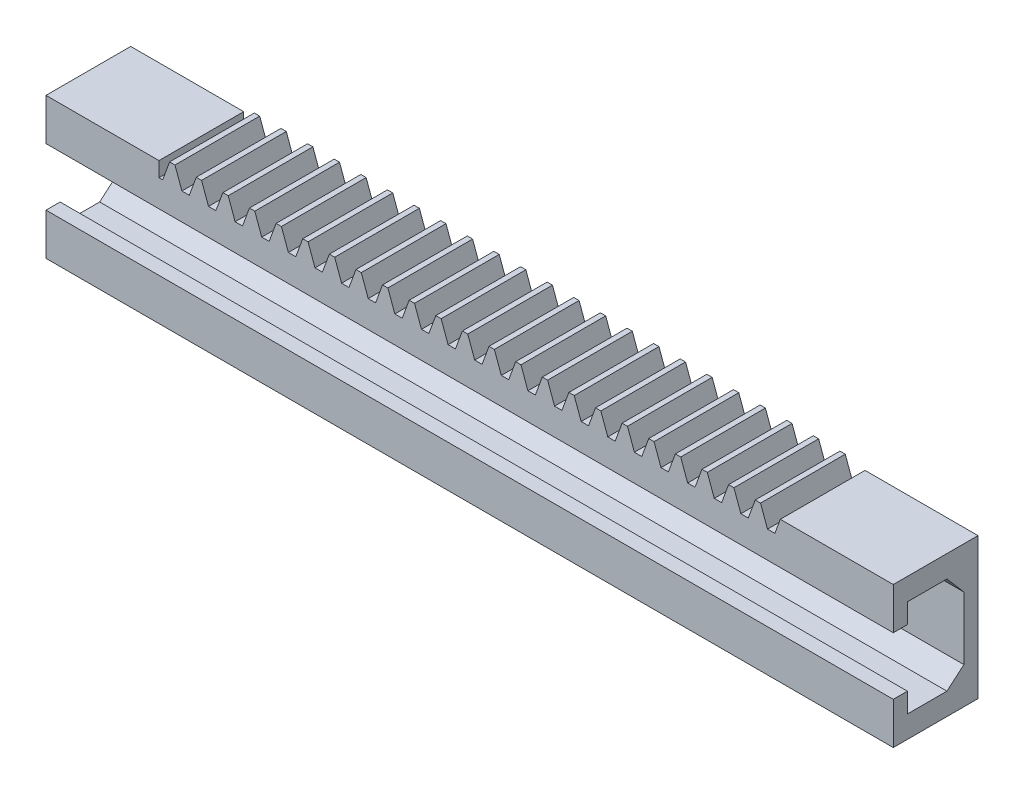
SolidWorks part; units mm, degrees
extrude "Blank" add sketch "BlankSke" against normal blind 15
sketch "BlankSke" plane through (0, 0, 0) normal (0, 0, 1) x (1, 0, 0)
  line L1 (0, 0) -> (110, 0)
  line L2 (0, 0) -> (0, 11.5)
  line L3 (0, 11.5) -> (110, 11.5)
  line L4 (110, 0) -> (110, 11.5)
  dimension "Length" = 110
ref_plane "Plane1" through (0, 0, 0) normal (0, 0, 1) x (1, 0, 0)
ref_plane "Plane2" through (0, 0, 0) normal (0, 1, 0) x (1, 0, 0)
ref_plane "Plane3" through (0, 0, 0) normal (1, 0, 0) x (0, 0, -1)
other "Configuration Table"
sketch "HoldingSke" plane through (0, 0, 0) normal (0, 1, 0) x (1, 0, 0)
  line L0 (0, 0) -> (0.0928, 0.6602)
  line L1 (-15, 0) -> (100, 0) construction
  line L2 (0, 0) -> (-2.1039, 2.3779)
  line L3 (0, 0) -> (-11.863, 4.5341)
  line L4 (0, 0) -> (7.8269, 3.6497)
  line L5 (0, 0) -> (-23.7986, -8.8762)
  line L6 (0, 0) -> (-10.5278, -7.1032)
  line L9 (-71.009, 38.7566) -> (32.3572, 76.3788)
  line L10 (-76.2, 3.8779) -> (-66.2, 3.8779)
  line L11 (0, 0) -> (-15, 0)
  line L12 (-76.2, 101.6) -> (-76.147, 101.6)
  line L13 (24.9733, 27.94) -> (52.9518, 28.4284)
  line L14 (24.9733, 27.94) -> (24.9743, 27.94)
  line L15 (24.9733, 27.94) -> (100.4006, 29.5858)
  circle A0 centre (0, 0) radius 19.05
  circle A1 centre (0, 0) radius 5
  circle A2 centre (0, 0) radius 12.7
  dimension "Num_teeth" = 25
  dimension "Width" = 15
  dimension "Length" = 110
  dimension "Pitch_height" = 10
sketch "TooCutSkeIll" plane through (0, 0, 0) normal (0, 0, 1) x (1, 0, 0)
  line L0 (-1.8687, 11.4605) -> (-0.7447, 8.3724)
  line L1 (-0.3914, 8.125) -> (0.3914, 8.125)
  line L2 (0.7447, 8.3724) -> (1.8687, 11.4605)
  line L3 (110, 11.5) -> (0, 11.5) construction
  line L4 (0, 0) -> (0, 64.897) construction
  line L5 (-13.208, 10) -> (12.954, 10) construction
  line L6 (0, 0) -> (110, 0) construction
  line L7 (1.3371, 10) -> (1.3371, 48.7463) construction
  line L8 (-1.3371, 10) -> (-1.3371, 48.7463) construction
  line L9 (1.9251, 11.5) -> (1.9251, 11.5254)
  line L10 (-1.9251, 11.5) -> (-1.9251, 11.5254)
  line L11 (-1.9251, 11.5254) -> (1.9251, 11.5254)
  arc A0 (0.3914, 8.125) -> (0.7447, 8.3724) centre (0.3914, 8.501) ccw
  arc A1 (-0.7447, 8.3724) -> (-0.3914, 8.125) centre (-0.3914, 8.501) ccw
  arc A2 (1.9251, 11.5) -> (1.8687, 11.4605) centre (1.9251, 11.44) ccw
  arc A3 (-1.8687, 11.4605) -> (-1.9251, 11.5) centre (-1.9251, 11.44) ccw
  dimension "Addendum_plus" = 1.5254
  dimension "Pitch_height" = 10
  dimension "Pressure_angle" = 20
  dimension "Gap_width" = 2.6742
  dimension "Dedendum" = 1.875
extrude "ToothCutIll" [suppressed] cut sketch "TooCutSkeIll" against normal through all
sketch "TooCutSkeSim" plane through (0, 0, 0) normal (0, 0, 1) x (1, 0, 0)
  line L0 (0.6547, 8.125) -> (-0.6547, 8.125)
  line L1 (1.8923, 11.5254) -> (0.6547, 8.125)
  line L2 (0, 17.4625) -> (0, 53.467) construction
  line L3 (1.8923, 11.5254) -> (-1.8923, 11.5254)
  line L6 (-1.8923, 11.5254) -> (-0.6547, 8.125)
  line L9 (-1.3371, 10) -> (1.3371, 10) construction
  line L10 (0, 0) -> (110, 0) construction
  line L11 (1.3371, 10) -> (1.3371, 53.467) construction
  line L12 (-1.3371, 10) -> (-1.3371, 53.467) construction
  dimension "Addendum_plus" = 1.5254
  dimension "Pitch_height" = 10
  dimension "Pressure_angle" = 20
  dimension "Gap_width" = 2.6742
  dimension "Dedendum" = 1.875
extrude "ToothCutSim" cut sketch "TooCutSkeSim" against normal through all
pattern_linear "TeethCuts" count 25 spacing 4.7124 along (1, 0, 0) of "ToothCutIll", "ToothCutSim"
sketch "Sketch1" plane through (110, 0, 0) normal (1, 0, 0) x (0, 0, -1)
  line L1 (0, 10.7637) -> (15, 10.7637)
  line L2 (0, 10.7637) -> (0, 0)
  line L3 (0, 0) -> (15, 0)
  line L4 (15, 10.7637) -> (15, 0)
extrude "Boss-Extrude1" add sketch "Sketch1" along normal blind 20
sketch "Sketch4" plane through (0, 0, 0) normal (-1, 0, 0) x (0, 0, 1)
  line L0 (-15, 8.125) -> (-15, 11.5) construction
  line L1 (0, 0) -> (-15, 0)
  line L2 (0, 0) -> (0, 10.764)
  line L3 (0, 10.764) -> (-15, 10.764)
  line L4 (-15, 0) -> (-15, 10.764)
extrude "Boss-Extrude2" add sketch "Sketch4" along normal blind 20
sketch "Sketch5" plane through (0, 0, 0) normal (0, -1, 0) x (1, 0, 0)
  line L1 (-20, -15) -> (130, -15)
  line L2 (-20, -15) -> (-20, 0)
  line L3 (-20, 0) -> (130, 0)
  line L4 (130, -15) -> (130, 0)
extrude "Boss-Extrude3" add sketch "Sketch5" along normal blind 14.236
sketch "Sketch7" plane through (-20, 0, 0) normal (-1, 0, 0) x (0, 0, 1)
  line L0 (-2.5, -6.836) -> (-2.5, -10.336)
  line L2 (-9.5, -10.336) -> (-7.5, -10.336)
  line L5 (-7.5, -10.336) -> (-2.5, -10.336)
  line L7 (0, -6.836) -> (0, 3.364)
  line L8 (-2.5, 6.864) -> (-9.5, 6.864)
  line L9 (-15, 10.764) -> (-15, -14.236) construction
  line L10 (-15, 6.864) -> (-15, -10.336)
  line L13 (0, 3.364) -> (-2.5, 3.364)
  line L14 (-2.5, 3.364) -> (-2.5, 6.864)
  line L15 (-2.5, 6.864) -> (-2.5, 3.364)
  line L18 (0, -6.836) -> (-2.5, -6.836)
  line L21 (-12.5, -1.736) -> (-12.5, 3.364)
  line L22 (-12.5, 3.364) -> (-12.5, -7.7646)
  line L24 (-9.5, 6.864) -> (-12.5, 3.364)
  line L25 (-9.5, -10.336) -> (-12.5, -7.7646)
  line M7 (0, -14.236) -> (0, 10.764)
extrude "Cut-Extrude1" cut sketch "Sketch7" against normal through all both and the other way through all contours L25 L2 L5 L0 L18 L13 L14 L8 L24 L21 L22 M7 region at (-20, -1.7846, -6.4607)
equation "' \"Module@HoldingSke\" = 6.35"
equation "' \"Num_teeth@HoldingSke\" = 12"
equation "' \"Ap@HoldingSke\" =  20"
equation "' \"Ap@HoldingSke\" = 20"
equation "' \"Width@HoldingSke\" = 0.25 * 25.4"
equation "' \"Show_teeth@HoldingSke\" = 500"
equation "' \"Backlash@HoldingSke\" = 0.009 * 25.4"
equation "' \"Addendum_fac@HoldingSke\" = 1.0"
equation "' \"Dedendum_fac@HoldingSke\" = 1.25"
equation "' \"Dedendum_add@HoldingSke\" = 0.00005 * 25.4"
equation "' \"Clearance_fac@HoldingSke\" = 0.25"
equation "' \"Pitch_height@HoldingSke\" = 1 * 25.4"
equation "' \"Length@HoldingSke\" = 4.71 * 25.4"
equation "\"Pitch@HoldingSke\" = 1 / \"Module@HoldingSke\""
equation "\"MPH@HoldingSke\" = \"Dedendum_fac@HoldingSke\" / \"Pitch@HoldingSke\" + 2 * \"Dedendum_add@HoldingSke\" + 0.002 * 25.4"
equation "\"MPH@HoldingSke\" = ((sgn( \"MPH@HoldingSke\" - \"Pitch_height@HoldingSke\")+1)*( \"MPH@HoldingSke\" - \"Pitch_height@HoldingSke\"))/2 + \"Pitch_height@HoldingSke\""
equation "\"Blank_height@BlankSke\" = \"Pitch_height@HoldingSke\" + \"Addendum_fac@HoldingSke\"  / \"Pitch@HoldingSke\" "
equation "\"Length@BlankSke\" =  \"Length@HoldingSke\""
equation "\"Face_width@Blank\" = \"Width@HoldingSke\""
equation "\"Pressure_angle@TooCutSkeIll\" = \"Ap@HoldingSke\""
equation "\"Addendum_plus@TooCutSkeIll\" =  \"Addendum_fac@HoldingSke\"  / \"Pitch@HoldingSke\" + 0.001 *25.4"
equation "\"Dedendum@TooCutSkeIll\" = \"Dedendum_fac@HoldingSke\"  / \"Pitch@HoldingSke\""
equation "\"Pitch_height@TooCutSkeIll\" =  \"MPH@HoldingSke\""
equation "\"Gap_width@TooCutSkeIll\" = 3.14159265 / 2 / \"Pitch@HoldingSke\" + 6 * \"Backlash@HoldingSke\""
equation "\"Pressure_angle@TooCutSkeSim\" = \"Ap@HoldingSke\""
equation "\"Addendum_plus@TooCutSkeSim\" =  \"Addendum_fac@HoldingSke\"  / \"Pitch@HoldingSke\" + 0.001 * 25.4"
equation "\"Dedendum@TooCutSkeSim\" = \"Dedendum_fac@HoldingSke\"  / \"Pitch@HoldingSke\""
equation "\"Pitch_height@TooCutSkeSim\" =  \"MPH@HoldingSke\""
equation "\"Gap_width@TooCutSkeSim\" = 3.14159265 / 2 / \"Pitch@HoldingSke\" + 6 * \"Backlash@HoldingSke\""
equation "\"Root_fillet@TooCutSkeIll\" = \"Clearance_fac@HoldingSke\" / \"Pitch@HoldingSke\" + \"Dedendum_add@HoldingSke\""
equation "\"Break_rad@TooCutSkeIll\" = 0.02 / \"Pitch@HoldingSke\" * 2"
equation "\"Linear_pitch@TeethCuts\" = 3.14159265 / \"Pitch@HoldingSke\""
equation "\"Num_teeth@HoldingSke\" = int( ( \"Length@HoldingSke\" + 0 ) / (3.14159265 / \"Pitch@HoldingSke\")) + 0.9999  + 1"
equation " \"Num_teeth@TeethCuts\" = int( \"Show_teeth@HoldingSke\" ) + 1"
equation " \"Num_teeth@TeethCuts\" = ((sgn( \"Num_teeth@TeethCuts\" - \"Num_teeth@HoldingSke\" )-1)*( \"Num_teeth@TeethCuts\" - \"Num_teeth@HoldingSke\" ))/-2+ \"Num_teeth@HoldingSke\""
equation " \"Num_teeth@TeethCuts\" = ((sgn( \"Num_teeth@TeethCuts\" - 2.0)+1)*( \"Num_teeth@TeethCuts\" - 2.0))/2 +2.0"
